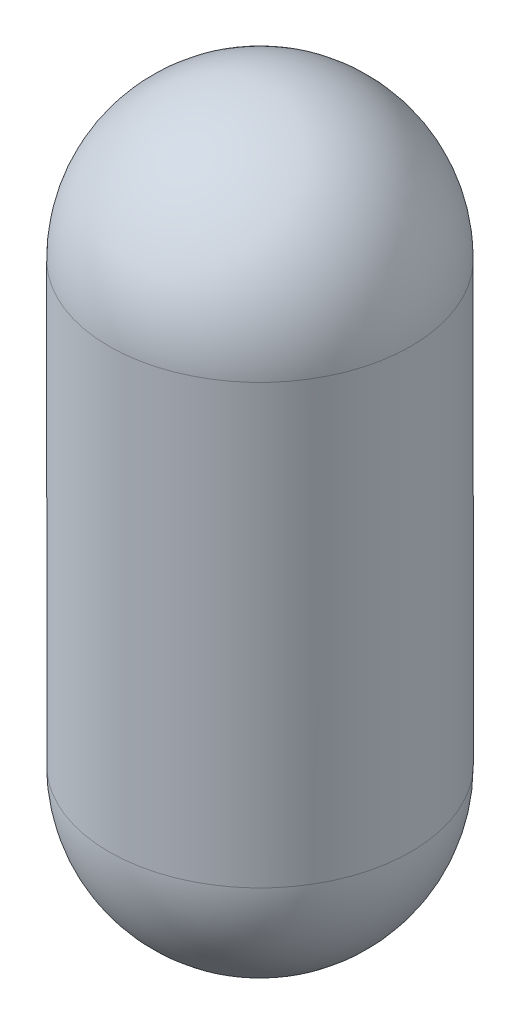
SolidWorks part; units mm, degrees
material "Ti-6Al-4VSolution treated and aged (SS)"
ref_plane "Front Plane" through (0, 0, 0) normal (0, 0, 1) x (1, 0, 0)
ref_plane "Top Plane" through (0, 0, 0) normal (0, 1, 0) x (1, 0, 0)
ref_plane "Right Plane" through (0, 0, 0) normal (1, 0, 0) x (0, 0, -1)
sketch "Sketch1" plane through (0, 0, 0) normal (0, 0, 1) x (1, 0, 0)
  line L4 (-510, -510) -> (-510, -1990)
  line L5 (0, 0) -> (0, -2500)
  arc A0 (0, 0) -> (-510, -510) centre (0, -510) ccw
  arc A1 (0, -2500) -> (-510, -1990) centre (0, -1990) cw
revolve "Revolve1" add sketch "Sketch1" angle 360 about L5
shell "Shell1" thickness 0.77
